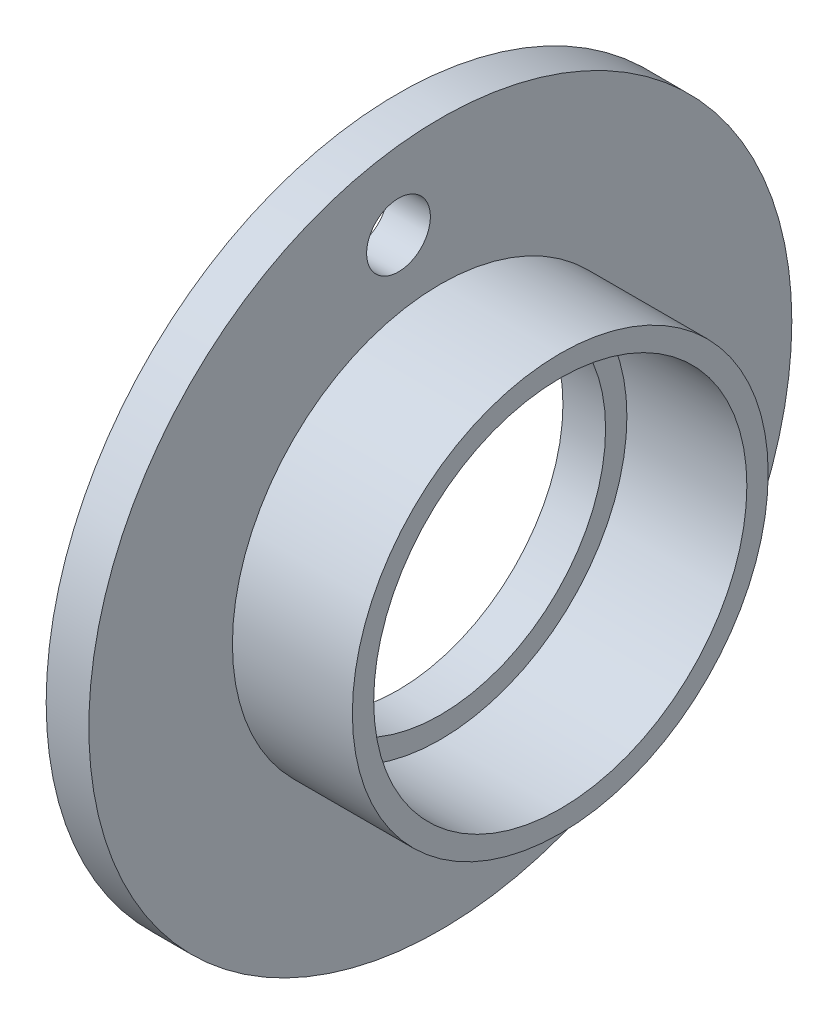
SolidWorks part; units mm, degrees
material "6061-T6 (SS)"
ref_plane "Front Plane" through (0, 0, 0) normal (0, 0, 1) x (1, 0, 0)
ref_plane "Top Plane" through (0, 0, 0) normal (0, 1, 0) x (1, 0, 0)
ref_plane "Right Plane" through (0, 0, 0) normal (1, 0, 0) x (0, 0, -1)
sketch "Sketch1" plane through (0, 0, 0) normal (0, 0, 1) x (1, 0, 0)
  line L0 (23.3719, 12.3825) -> (30.5156, 12.3825)
  line L1 (30.5156, 12.3825) -> (30.5156, 11.1125)
  line L2 (30.5156, 11.1125) -> (23.3719, 11.1125)
  line L4 (23.3719, 11.1125) -> (23.3719, 12.3825)
  line L5 (0, 0) -> (40.0174, 0) construction
  dimension "D1" = 22.225
  dimension "D2" = 7.1437
revolve "Revolve1" add sketch "Sketch1" angle 360 about L5
sketch "Sketch2" plane through (23.3719, 0, 0) normal (1, 0, 0) x (0, 0, -1)
  line L0 (0, 0) -> (-2.4917, 16.1603) construction
  line L1 (-7.0209, 15.4619) -> (2.0375, 16.8586) construction
  line L2 (-10.9827, -1.6934) -> (10.9827, 1.6934) construction
  line L4 (-4.1515, 11.8887) -> (0.3777, 12.5871) construction
  line L5 (0.3777, 12.5871) -> (2.0375, 16.8586) construction
  line L6 (2.0375, 16.8586) -> (-0.8319, 20.4319) construction
  line L7 (-0.8319, 20.4319) -> (-5.3611, 19.7335) construction
  line L8 (-5.3611, 19.7335) -> (-7.0209, 15.4619) construction
  line L9 (-7.0209, 15.4619) -> (-4.1515, 11.8887) construction
  arc A0 (-9.1674, 8.3237) -> (-6.2344, -10.6985) centre (0, 0) ccw
  circle A1 centre (0, 0) radius 12.3825 construction
  arc A7 (2.0375, 16.8586) -> (-7.0209, 15.4619) centre (-2.4917, 16.1603) ccw
  arc A8 (-9.1674, 8.3237) -> (-7.0209, 15.4619) centre (-15.5764, 14.1428) ccw
  arc A9 (2.0375, 16.8586) -> (6.2344, 10.6985) centre (10.5929, 18.1778) ccw
  circle A10 centre (0, 0) radius 9.8425
  circle A11 centre (0, 0) radius 11.1125 construction
  arc A16 (9.1674, -8.3237) -> (6.2344, 10.6985) centre (0, 0) ccw
  circle A17 centre (-2.4917, 16.1603) radius 3.9688 construction
  circle A18 centre (-2.4917, 16.1603) radius 2.1526 construction
  circle A19 centre (-2.4917, 16.1603) radius 2.1526 construction
  circle A20 centre (0, 0) radius 11.1125 construction
  arc A21 (7.0209, -15.4619) -> (9.1674, -8.3237) centre (15.5764, -14.1428) cw
  arc A22 (-6.2344, -10.6985) -> (-2.0375, -16.8586) centre (-10.5929, -18.1778) cw
  arc A23 (7.0209, -15.4619) -> (-2.0375, -16.8586) centre (2.4917, -16.1603) cw
  dimension "D1" = 1.27
  dimension "D3" = 7.9375
extrude "Boss-Extrude1" add sketch "Sketch2" against normal blind 2.54
hole_wizard "#6 Clearance Hole1" positions "Sketch3" profile "Sketch5" hole size "#6" standard "ANSI Inch" end condition up to next
sketch "Sketch3" plane through (20.8319, 0, 0) normal (-1, 0, 0) x (0, 0, 1)
  arc A0 (-7.0209, -15.4619) -> (2.0375, -16.8586) centre (-2.4917, -16.1603) ccw construction
  point P0 (2.4917, 16.1603)
  point P3 (-2.4917, -16.1603)
sketch "Sketch5" plane through (20.8319, 16.1603, 2.4917) normal (0, 1, 0) x (0, 0, 1)
  line L0 (0, 0) -> (0, 2.54)
  line L1 (0, 2.54) -> (1.8986, 2.54)
  line L2 (1.8986, 2.54) -> (1.8986, 0)
  line L5 (1.8986, 0) -> (0, 0)
  line L11 (0, -6.35) -> (0, 107.95) construction
  dimension "Thru Hole Dia." = 3.7973
  dimension "Thru Hole Depth" = 2.54
sketch "Sketch6" plane through (23.3719, 0, 0) normal (1, 0, 0) x (0, 0, -1)
  circle A0 centre (0, 0) radius 12.3825
  circle A2 centre (0, 0) radius 12.3825 construction
  circle A3 centre (0, 0) radius 20.934
  arc A4 (2.0375, 16.8586) -> (-7.0209, 15.4619) centre (-2.4917, 16.1603) ccw construction
  circle A5 centre (2.4917, -16.1603) radius 1.8986 construction
  circle A6 centre (-2.4917, 16.1603) radius 1.8986 construction
  circle A7 centre (2.4917, -16.1603) radius 1.8986
  circle A8 centre (-2.4917, 16.1603) radius 1.8986
extrude "Boss-Extrude2" add sketch "Sketch6" against normal up to surface (2.54 mm away) up to face at (20.8319, 16.1603, 4.3904)
